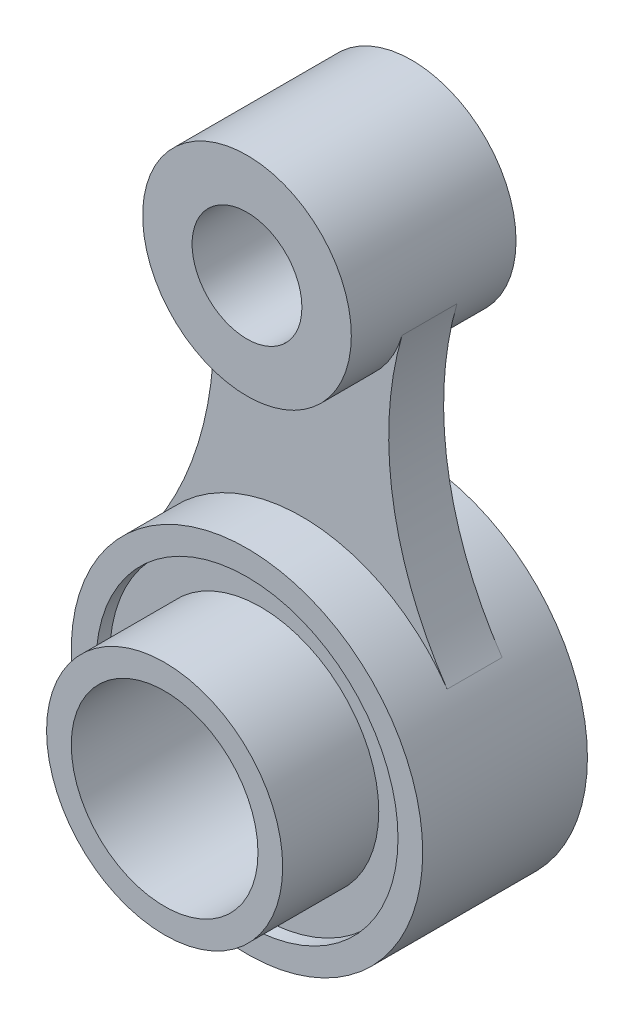
SolidWorks part; units mm, degrees
note: The reader was unsure of these and kept them because the rebuilt part matched: shared geometry of "Sketch2<3>", "Sketch2<5>", "Sketch2<6>", "Sketch2<7>".
ref_plane "Front Plane" through (0, 0, 0) normal (0, 0, 1) x (1, 0, 0)
ref_plane "Top Plane" through (0, 0, 0) normal (0, 1, 0) x (1, 0, 0)
ref_plane "Right Plane" through (0, 0, 0) normal (1, 0, 0) x (0, 0, -1)
sketch "Sketch2" plane through (0, 0, 0) normal (0, 0, 1) x (1, 0, 0)
  line L0 (-38.0752, 0) -> (69.6781, 0) construction
  line L1 (-38.0752, 75) -> (76.1537, 75) construction
  line L2 (7.9583, 140.7451) -> (7.9583, -86.7803) construction
  circle A1 centre (7.9583, 0) radius 27.5
  circle A2 centre (7.9583, 0) radius 21.5
  circle A3 centre (7.9583, 0) radius 32
  circle A4 centre (7.9583, 0) radius 17
  circle A5 centre (7.9583, 75) radius 19
  circle A6 centre (7.9583, 75) radius 10
  arc A7 (-18.7243, 17.6646) -> (-10.3644, 69.972) centre (-72.1323, 53.0222) ccw
  arc A8 (26.2042, 69.7005) -> (34.4123, 18.0051) centre (85.1929, 52.5673) ccw
  point P8 (-72.0654, 52.7802)
  point P21 (-76.2435, 62.6958)
  point P22 (-81.6599, 55.5103)
  point P23 (89.5613, 53.71)
  point P24 (-73.2588, 53.71)
  point P25 (85.2544, 52.7802)
  dimension "D2" = 64
  dimension "D3" = 55
  dimension "D4" = 43
  dimension "D5" = 34
  dimension "D6" = 38
  dimension "D7" = 20
  dimension "D1" = 75
extrude "Boss-Extrude1" add sketch "Sketch2" along normal mid plane 10 contours A8 A5 A7 A3
extrude "Boss-Extrude2" add sketch "Sketch2<3>" along normal mid plane 30 contours A5 A6
sketch "Sketch2<3>" plane through (0, 0, 0) normal (0, 0, 1) x (1, 0, 0) same geometry as "Sketch2"
extrude "Boss-Extrude3" add sketch "Sketch2<5>" along normal mid plane 30 contours A3 A1
sketch "Sketch2<5>" plane through (0, 0, 0) normal (0, 0, 1) x (1, 0, 0) same geometry as "Sketch2"
extrude "Boss-Extrude4" add sketch "Sketch2<6>" along normal blind 30 and the other way blind 15 separate body contours A2 A4
sketch "Sketch2<6>" plane through (0, 0, 0) normal (0, 0, 1) x (1, 0, 0) same geometry as "Sketch2"
extrude "Boss-Extrude5" add sketch "Sketch2<7>" along normal mid plane 25 contours A1 A2
sketch "Sketch2<7>" plane through (0, 0, 0) normal (0, 0, 1) x (1, 0, 0) same geometry as "Sketch2"
